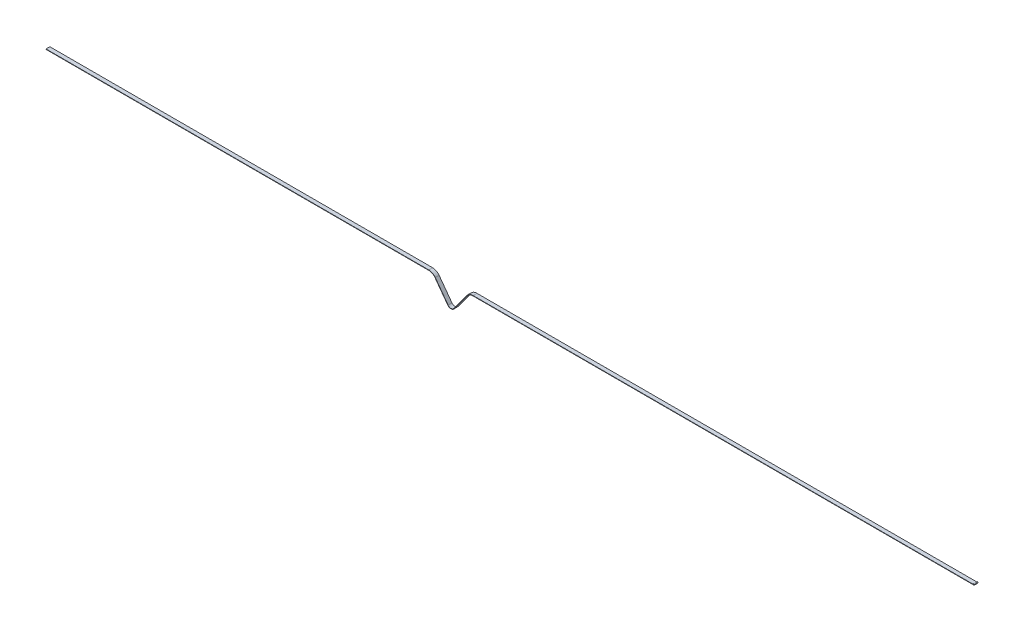
SolidWorks part; units mm, degrees
material "BUTYL"
ref_plane "Front Plane" through (0, 0, 0) normal (0, 0, 1) x (1, 0, 0)
ref_plane "Top Plane" through (0, 0, 0) normal (0, 1, 0) x (1, 0, 0)
ref_plane "Right Plane" through (0, 0, 0) normal (1, 0, 0) x (0, 0, -1)
sketch "Sketch1" plane through (0, 0, 0) normal (1, 0, 0) x (0, 0, -1)
  line L1 (0, 0) -> (6, 0)
  line L2 (0, 0) -> (0, 0.63)
  line L3 (0, 0.63) -> (6, 0.63)
  line L4 (6, 0) -> (6, 0.63)
  dimension "D1" = 0.63
  dimension "D2" = 6
sketch "Sketch2" plane through (0, 0, 0) normal (0, 0, 1) x (1, 0, 0)
  line L0 (0, 0) -> (-781.5813, 0)
  line L1 (-791.214, -4.8779) -> (-811.2262, -32.1359)
  line L2 (-821.0765, -32.1359) -> (-841.0887, -4.8779)
  line L3 (-850.7213, 0) -> (-1447.8, 0)
  arc A0 (-781.5813, 0) -> (-791.214, -4.8779) centre (-781.5813, -11.95) ccw
  arc A1 (-811.2262, -32.1359) -> (-821.0765, -32.1359) centre (-816.1513, -28.52) cw
  arc A2 (-841.0887, -4.8779) -> (-850.7213, 0) centre (-850.7213, -11.95) ccw
  circle A3 centre (-816.1513, -28.52) radius 8 construction
  circle A4 centre (-781.5813, -11.95) radius 11.95 construction
  circle A5 centre (-850.7213, -11.95) radius 11.95 construction
  dimension "D1" = 6.11
  dimension "D4" = 1447.8
sweep "Sweep1" add profiles "Sketch1" path "Sketch2"
sketch "Sketch3" plane through (0, 0, 0) normal (0, 0, 1) x (1, 0, 0)
  line L0 (0, 0.63) -> (-781.5813, 0.63) construction
  line L1 (-1.5, 0.63) -> (-1.5, 0)
  line L2 (0, 0) -> (-781.5813, 0) construction
  line L3 (-1.5, 0) -> (0, 0)
  line L4 (0, 0) -> (0, 0.63)
  arc A1 (0, 0.63) -> (-1.5, 0.63) centre (-0.75, 0.63) ccw
  dimension "D1" = 0.75
extrude "Boss-Extrude1" add sketch "Sketch3" against normal through all
pattern_curve "CrvPattern1" [suppressed] of bodies 102 driven by "Sketch2" parameters "D1"=2000, "D3"=2, "D2"=1, "D4"=10
